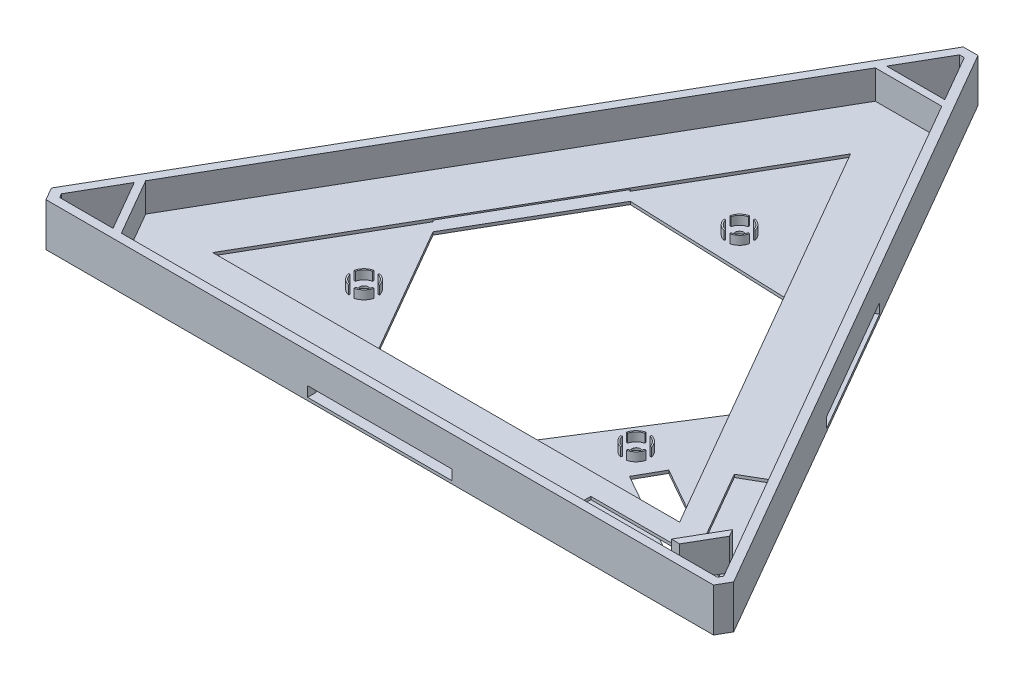
SolidWorks part; units mm, degrees
ref_plane "Front Plane" through (0, 0, 0) normal (0, 0, 1) x (1, 0, 0)
ref_plane "Top Plane" through (0, 0, 0) normal (0, 1, 0) x (1, 0, 0)
ref_plane "Right Plane" through (0, 0, 0) normal (1, 0, 0) x (0, 0, -1)
sketch "Sketch1" plane through (0, 0, 0) normal (0, 1, 0) x (1, 0, 0)
  line L0 (351.2729, 67.6655) -> (468.273, -134.9846)
  line L1 (347.2728, 67.6655) -> (347.2728, 65.1655) construction
  line L2 (409.773, -33.6595) -> (407.6079, -34.9095) construction
  line L3 (468.273, -134.9846) -> (464.2732, -141.9124)
  line L4 (230.2733, -141.9124) -> (464.2732, -141.9124)
  line L5 (230.2733, -141.9124) -> (226.2727, -134.9842)
  line L6 (226.2727, -134.9842) -> (343.2728, 67.6655)
  line L7 (353.4142, 63.9567) -> (351.2491, 62.7067) construction
  line L8 (347.2733, -141.9124) -> (347.2733, -139.4124) construction
  line L9 (231.7167, -139.4124) -> (462.8299, -139.4124)
  line L10 (284.7727, -33.6594) -> (286.9378, -34.9094) construction
  line L11 (344.7161, 65.1655) -> (349.8295, 65.1655)
  line L12 (465.3862, -134.9846) -> (349.8295, 65.1655)
  line L13 (466.2731, -138.4485) -> (464.1081, -137.1985) construction
  line L14 (462.8299, -139.4124) -> (465.3862, -134.9846)
  line L15 (229.1594, -134.9842) -> (344.7161, 65.1655)
  line L16 (229.1594, -134.9842) -> (231.7167, -139.4124)
  line L17 (286.9378, -34.9094) -> (287.3708, -35.1594) construction
  line L18 (230.438, -137.1983) -> (230.871, -136.9483) construction
  line L19 (232.0053, -138.9123) -> (229.7368, -134.9842)
  line L20 (343.2728, 67.6655) -> (351.2729, 67.6655)
  line L21 (345.0048, 64.6655) -> (229.7368, -134.9842)
  line L22 (349.5409, 64.6655) -> (345.0048, 64.6655)
  line L23 (249.0568, -126.4468) -> (246.8918, -127.697) construction
  line L24 (407.6079, -34.9095) -> (407.1749, -35.1595) construction
  line L26 (233.4463, -136.4089) -> (251.9226, -136.4093)
  line L27 (464.8089, -134.9846) -> (462.5412, -138.9123)
  line L28 (462.5412, -138.9123) -> (232.0053, -138.9123)
  line L29 (251.9226, -136.4093) -> (241.8609, -118.9847)
  line L30 (241.8609, -118.9847) -> (232.6236, -134.9842)
  line L31 (232.6236, -134.9842) -> (233.4463, -136.4089)
  line L33 (287.3708, -35.1594) -> (289.5359, -36.4094) construction
  line L34 (254.8093, -136.4089) -> (243.3042, -116.4848)
  line L35 (335.7675, 43.666) -> (243.3042, -116.4848)
  line L36 (358.7782, 43.666) -> (335.7675, 43.666)
  line L38 (289.5359, -36.4094) -> (306.8564, -46.4094) construction
  line L41 (461.939, -134.9846) -> (461.1164, -136.4093)
  line L42 (347.2688, -136.4172) -> (347.2688, -116.4172) construction
  line L43 (442.6021, -136.4093) -> (452.6999, -118.9847)
  line L44 (245.2636, -119.878) -> (249.0568, -126.4468) construction
  line L45 (452.6999, -118.9847) -> (461.939, -134.9846)
  line L48 (461.1164, -136.4093) -> (442.6021, -136.4093)
  line L49 (405.0134, -36.4027) -> (387.6936, -46.404) construction
  line L50 (306.8564, -46.4094) -> (466.2731, -138.4485) construction
  line L51 (357.3348, 46.166) -> (337.2109, 46.166)
  line L52 (337.2109, 46.166) -> (346.4484, 62.1659)
  line L53 (346.4484, 62.1659) -> (348.0966, 62.164)
  line L54 (348.0966, 62.164) -> (357.3348, 46.166)
  line L55 (228.273, -138.4483) -> (387.6936, -46.404) construction
  line L56 (347.2688, -116.4172) -> (347.2728, 43.666) construction
  line L57 (266.4391, -116.428) -> (428.1137, -116.4172)
  line L58 (347.2736, 23.6092) -> (428.1137, -116.4172)
  line L59 (266.4391, -116.428) -> (347.2736, 23.6092)
  line L60 (439.7283, -136.4254) -> (439.7283, -132.9254) construction
  line L61 (451.2487, -116.4715) -> (448.6507, -117.9717) construction
  line L62 (452.6999, -118.9847) -> (358.7782, 43.666)
  line L63 (442.6021, -136.4093) -> (254.8093, -136.4089)
  line L64 (441.749, -132.9254) -> (444.621, -132.9254)
  line L65 (448.6507, -117.9717) -> (450.9647, -121.979) construction
  line L66 (449.5167, -119.4714) -> (450.9647, -121.979)
  line L67 (441.749, -132.9254) -> (449.5167, -119.4714)
  line L68 (450.9647, -121.979) -> (444.621, -132.9254)
  line L69 (461.939, -134.9846) -> (427.2809, -114.9747) construction
  line L70 (461.1164, -136.4093) -> (426.4891, -116.4173) construction
  line L73 (405.0134, -134.9846) -> (439.7283, -134.9846)
  line L74 (405.0134, -134.9846) -> (405.0134, -124.0609)
  line L75 (405.0134, -124.0609) -> (439.7283, -124.0609)
  line L76 (439.7283, -134.9846) -> (439.7283, -124.0609)
  line L77 (405.0134, -124.0609) -> (430.3202, -80.2282) construction
  line L78 (405.0134, -134.9846) -> (433.4739, -85.6896) construction
  line L79 (461.1164, -136.4093) -> (424.3464, -72.7321) construction
  line L80 (432.6513, -87.1143) -> (423.1904, -92.5775)
  line L81 (432.6513, -87.1143) -> (450.1194, -117.365)
  line L82 (423.1904, -92.5775) -> (440.6585, -122.8281)
  line L83 (450.1194, -117.365) -> (440.6585, -122.8281)
  point P13 (407.6079, -34.9095)
  point P20 (464.1081, -137.1985)
  point P23 (347.2733, -139.4124)
  point P25 (347.2732, -141.9124)
  point P27 (347.2728, 65.1655)
  point P31 (286.9378, -34.9094)
  point P37 (287.3708, -35.1594)
  point P39 (230.871, -136.9483)
  point P41 (347.2728, 64.6655)
  point P45 (407.1749, -35.1595)
  point P50 (246.8918, -127.697)
  point P56 (289.5359, -36.4094)
  point P58 (249.0568, -126.4468)
  point P60 (347.2728, 43.666)
  point P62 (345.0048, -136.4089)
  point P64 (445.4885, -126.4485)
  point P71 (447.651, -127.697)
  point P77 (347.2728, 46.166)
  point P84 (347.2688, -116.4172)
  point P87 (387.6936, -46.404)
  point P89 (306.8564, -46.4094)
  point P100 (405.0134, -36.4027)
  dimension "D1" = 2.5
  dimension "D2" = 2.5
  dimension "D3" = 2.5
  dimension "D4" = 2.5
  dimension "D5" = 2.5
  dimension "D6" = 2.5
  dimension "D7" = 0.5
  dimension "D8" = 0.5
  dimension "D9" = 0.5
  dimension "D10" = 2.5
  dimension "D11" = 2.5
  dimension "D12" = 20
  dimension "D13" = 20
  dimension "D14" = 20
  dimension "D15" = 3.5
  dimension "D16" = 3
extrude "Boss-Extrude1" add sketch "Sketch1" along normal blind 1 contours L36 L35 L34 L57 L59 L58 region at (251.4484, 0, 125.0658)
extrude "Boss-Extrude2" add sketch "Sketch1<9>" along normal blind 11 contours L28 L27 L22 L21 L19 L31 L30 L29 L26 L34 L35 L36 L41 L48 L43 L45 L53 L54 L51 L52 | L68 L64 L67 L66 region at (230.7087, 0, 137.042)
sketch "Sketch1<9>" plane through (0, 0, 0) normal (0, 1, 0) x (1, 0, 0) same geometry as "Sketch1"
extrude "Boss-Extrude3" add sketch "Sketch1<10>" along normal blind 5 and the other way blind 3 contours L28 L27 L22 L21 L19 L31 L30 L29 L26 L34 L35 L36 L41 L48 L43 L45 L53 L54 L51 L52 region at (230.7087, 0, 137.042)
sketch "Sketch1<10>" plane through (0, 0, 0) normal (0, 1, 0) x (1, 0, 0) same geometry as "Sketch1"
sketch "Sketch3" plane through (290.5896, 0, -167.772) normal (0.866, 0, -0.5) x (-0.5, 0, -0.866)
  line L1 (-261.593, -6.5) -> (-211.593, -6.5)
  line L2 (-261.593, -6.5) -> (-261.593, 0.5)
  line L3 (-261.593, 0.5) -> (-211.593, 0.5)
  line L4 (-211.593, -6.5) -> (-211.593, 0.5)
  line L5 (-261.593, -6.5) -> (-211.593, 0.5) construction
  line L6 (-261.593, 0.5) -> (-211.593, -6.5) construction
  point P0 (-236.593, -3)
  dimension "D1" = 50
  dimension "D2" = 7
extrude "Cut-Extrude3" cut sketch "Sketch3" against normal blind 25
sketch "Sketch5" plane through (0, 0, 139.4124) normal (0, 0, 1) x (1, 0, 0)
  line L0 (231.7167, -3) -> (462.8299, -3) construction
  line L1 (322.2733, -6.5) -> (372.2733, -6.5)
  line L2 (322.2733, -6.5) -> (322.2733, 0.5)
  line L3 (322.2733, 0.5) -> (372.2733, 0.5)
  line L4 (372.2733, -6.5) -> (372.2733, 0.5)
  line L5 (322.2733, -6.5) -> (372.2733, 0.5) construction
  line L6 (322.2733, 0.5) -> (372.2733, -6.5) construction
  point P0 (347.2733, -3)
  dimension "D1" = 50
  dimension "D2" = 7
extrude "Cut-Extrude4" cut sketch "Sketch5" against normal blind 25
sketch "Sketch6" plane through (230.3194, 0, 132.9752) normal (-0.866, 0, -0.5) x (-0.5, 0, 0.866)
  line L0 (2.3199, -3) -> (-228.7932, -3) construction
  line L1 (-138.2367, -6.5) -> (-88.2367, -6.5)
  line L2 (-138.2367, -6.5) -> (-138.2367, 0.5)
  line L3 (-138.2367, 0.5) -> (-88.2367, 0.5)
  line L4 (-88.2367, -6.5) -> (-88.2367, 0.5)
  line L5 (-138.2367, -6.5) -> (-88.2367, 0.5) construction
  line L6 (-138.2367, 0.5) -> (-88.2367, -6.5) construction
  point P0 (-113.2367, -3)
  dimension "D1" = 50
  dimension "D2" = 7
extrude "Cut-Extrude5" cut sketch "Sketch6" against normal blind 25
sketch "Sketch8" plane through (0, -3, 0) normal (0, -1, 0) x (1, 0, 0)
  line L1 (349.8295, -65.1655) -> (465.3862, 134.9846)
  line L2 (465.3862, 134.9846) -> (462.8299, 139.4124)
  line L6 (462.8299, 139.4124) -> (231.7167, 139.4124)
  line L7 (450.147, 123.2807) -> (452.6999, 118.9847)
  line L9 (452.6999, 118.9847) -> (461.939, 134.9846)
  line L12 (461.939, 134.9846) -> (461.1164, 136.4093)
  line L17 (461.1164, 136.4093) -> (442.6021, 136.4093)
  line L19 (322.2733, 116.4243) -> (294.3582, 68.0611)
  line L20 (294.3582, 68.0611) -> (319.3545, 24.7577)
  line L21 (319.3545, 24.7577) -> (376.4737, 26.9694)
  line L22 (376.4737, 26.9694) -> (401.4727, 70.2712)
  line L23 (401.4727, 70.2712) -> (372.2733, 116.4209)
  line L24 (372.2733, 116.4209) -> (322.2733, 116.4243)
  line L25 (386.873, 93.3461) -> (395.3235, 98.6928) construction
  line L30 (308.3157, 92.2427) -> (299.6549, 97.2417) construction
  line L31 (347.9141, 25.8635) -> (348.3013, 15.8635) construction
  line L34 (401.698, 107.3846) -> (445.2267, 131.9864)
  line L35 (450.147, 123.2807) -> (406.6183, 98.6788)
  line L36 (401.698, 107.3846) -> (406.6183, 98.6788)
  line L37 (231.7167, 139.4124) -> (229.1594, 134.9842)
  line L39 (233.4463, 136.4089) -> (251.9226, 136.4093)
  line L40 (251.9226, 136.4093) -> (241.8609, 118.9847)
  line L41 (241.8609, 118.9847) -> (232.6236, 134.9842)
  line L42 (232.6236, 134.9842) -> (233.4463, 136.4089)
  line L43 (349.8295, -65.1655) -> (344.7161, -65.1655)
  line L44 (344.7161, -65.1655) -> (229.1594, 134.9842)
  line L45 (337.2109, -46.166) -> (357.3348, -46.166)
  line L46 (357.3348, -46.166) -> (348.0966, -62.164)
  line L47 (348.0966, -62.164) -> (346.4484, -62.1659)
  line L48 (346.4484, -62.1659) -> (337.2109, -46.166)
  line L49 (442.6021, 136.4093) -> (445.2267, 131.9864)
  circle A0 centre (395.3235, 98.6928) radius 1.5
  circle A1 centre (348.3013, 15.8635) radius 1.5
  circle A2 centre (299.6549, 97.2417) radius 1.5
  dimension "D6" = 3
  dimension "D7" = 3
  dimension "D8" = 3
  dimension "D1" = 10
  dimension "D2" = 50
  dimension "D3" = 10
  dimension "D4" = 10
  dimension "D5" = 10
extrude "Boss-Extrude5" add sketch "Sketch8" along normal blind 1
sketch "Sketch12" plane through (0, -3, 0) normal (0, 1, 0) x (1, 0, 0)
  line L0 (348.3013, -11.8635) -> (348.3013, -11.3635) construction
  line L1 (348.3013, -11.3635) -> (349.2951, -11.4746) construction
  line L2 (349.2951, -11.4746) -> (349.1847, -11.9623)
  line L3 (348.3013, -11.3635) -> (347.3075, -11.4746) construction
  line L4 (347.3075, -11.4746) -> (347.4179, -11.9623)
  line L5 (352.3013, -15.8635) -> (352.8013, -15.8635) construction
  line L6 (344.3013, -15.8635) -> (343.8013, -15.8635) construction
  line L7 (348.3013, -19.8635) -> (348.3013, -20.3635) construction
  line L8 (352.8013, -15.8635) -> (352.6902, -14.8697) construction
  line L9 (352.8013, -15.8635) -> (352.6902, -16.8573) construction
  line L10 (343.8013, -15.8635) -> (343.9124, -14.8697) construction
  line L11 (343.8013, -15.8635) -> (343.9124, -16.8573) construction
  line L12 (348.3013, -20.3635) -> (349.2951, -20.2524) construction
  line L13 (348.3013, -20.3635) -> (347.3075, -20.2524) construction
  line L14 (343.9124, -14.8697) -> (348.3013, -15.8635) construction
  line L15 (348.3013, -15.8635) -> (352.6902, -14.8697) construction
  line L16 (343.9124, -16.8573) -> (348.3013, -15.8635) construction
  line L17 (348.3013, -15.8635) -> (352.6902, -16.8573) construction
  line L18 (347.3075, -20.2524) -> (348.3013, -15.8635) construction
  line L19 (348.3013, -15.8635) -> (349.2951, -20.2524) construction
  line L20 (343.9124, -14.8697) -> (344.4001, -14.9801)
  line L21 (343.9124, -16.8573) -> (344.4001, -16.7469)
  line L22 (347.3075, -20.2524) -> (347.4179, -19.7648)
  line L23 (349.2951, -20.2524) -> (349.1847, -19.7648)
  line L24 (352.6902, -14.8697) -> (352.2025, -14.9801)
  line L25 (352.6902, -16.8573) -> (352.2025, -16.7469)
  line L26 (395.3235, -94.1928) -> (395.3235, -98.6928) construction
  line L27 (395.3235, -98.6928) -> (390.8235, -98.6928) construction
  line L28 (390.8235, -98.6928) -> (390.9347, -97.699) construction
  line L29 (399.8235, -98.6928) -> (395.3235, -98.6928) construction
  line L30 (395.3235, -98.6928) -> (395.3235, -103.1928) construction
  line L31 (395.3235, -103.1928) -> (396.3173, -103.0817) construction
  line L32 (395.3235, -94.1928) -> (396.3173, -94.3039) construction
  line L33 (395.3235, -94.1928) -> (394.3297, -94.3039) construction
  line L34 (399.7124, -97.699) -> (399.8235, -98.6928) construction
  line L35 (399.8235, -98.6928) -> (399.7124, -99.6866) construction
  line L36 (390.9347, -99.6866) -> (390.8235, -98.6928) construction
  line L37 (394.3297, -103.0817) -> (395.3235, -103.1928) construction
  line L38 (394.3297, -94.3039) -> (395.3235, -98.6928) construction
  line L39 (395.3235, -98.6928) -> (396.3173, -94.3039) construction
  line L40 (390.9347, -99.6866) -> (395.3235, -98.6928) construction
  line L41 (395.3235, -98.6928) -> (390.9347, -97.699) construction
  line L42 (399.7124, -97.699) -> (395.3235, -98.6928) construction
  line L43 (395.3235, -98.6928) -> (399.7124, -99.6866) construction
  line L44 (394.3297, -103.0817) -> (395.3235, -98.6928) construction
  line L45 (395.3235, -98.6928) -> (396.3173, -103.0817) construction
  line L46 (394.3297, -94.3039) -> (394.4402, -94.7916)
  line L47 (396.3173, -94.3039) -> (396.2069, -94.7916)
  line L48 (399.7124, -97.699) -> (399.2248, -97.8094)
  line L49 (399.7124, -99.6866) -> (399.2248, -99.5762)
  line L50 (396.3173, -103.0817) -> (396.2069, -102.5941)
  line L51 (394.3297, -103.0817) -> (394.4402, -102.5941)
  line L52 (390.9347, -99.6866) -> (391.4223, -99.5762)
  line L53 (390.9347, -97.699) -> (391.4248, -97.7985)
  line L54 (299.6549, -92.7417) -> (299.6549, -97.2417) construction
  line L55 (299.6549, -97.2417) -> (304.1549, -97.2417) construction
  line L56 (299.6549, -101.7417) -> (299.6549, -97.2417) construction
  line L57 (299.6549, -97.2417) -> (295.1549, -97.2417) construction
  line L58 (299.6549, -97.2417) -> (298.6611, -92.8528) construction
  line L59 (298.6611, -92.8528) -> (299.6549, -92.7417) construction
  line L60 (299.6549, -92.7417) -> (300.6487, -92.8528) construction
  line L61 (300.6487, -92.8528) -> (299.6549, -97.2417) construction
  line L62 (299.6549, -97.2417) -> (304.0438, -96.2479) construction
  line L63 (304.0438, -96.2479) -> (304.1549, -97.2417) construction
  line L64 (304.1549, -97.2417) -> (304.0438, -98.2355) construction
  line L65 (304.0438, -98.2355) -> (299.6549, -97.2417) construction
  line L66 (299.6549, -97.2417) -> (300.6487, -101.6306) construction
  line L67 (300.6487, -101.6306) -> (299.6549, -101.7417) construction
  line L68 (299.6549, -101.7417) -> (298.6611, -101.6306) construction
  line L69 (298.6611, -101.6306) -> (299.6549, -97.2417) construction
  line L70 (299.6549, -97.2417) -> (295.266, -98.2355) construction
  line L71 (295.266, -98.2355) -> (295.1549, -97.2417) construction
  line L72 (295.1549, -97.2417) -> (295.266, -96.2479) construction
  line L73 (295.266, -96.2479) -> (299.6549, -97.2417) construction
  line L74 (295.266, -96.2479) -> (295.7537, -96.3583)
  line L75 (295.266, -98.2355) -> (295.7537, -98.1251)
  line L76 (298.6611, -101.6306) -> (298.7715, -101.1429)
  line L77 (300.6487, -101.6306) -> (300.5383, -101.1429)
  line L78 (304.0438, -98.2355) -> (303.5561, -98.1251)
  line L79 (304.0438, -96.2479) -> (303.5561, -96.3583)
  line L80 (300.6487, -92.8528) -> (300.5383, -93.3404)
  line L81 (298.6611, -92.8528) -> (298.7715, -93.3404)
  circle A0 centre (348.3013, -15.8635) radius 4.5
  circle A1 centre (395.3235, -98.6928) radius 4.5
  circle A2 centre (299.6549, -97.2417) radius 4.5
  circle A3 centre (348.3013, -15.8635) radius 4
  circle A4 centre (395.3235, -98.6928) radius 4
  circle A5 centre (299.6549, -97.2417) radius 4
  dimension "D1" = 9
  dimension "D2" = 9
  dimension "D3" = 9
  dimension "D4" = 8
  dimension "D5" = 8
  dimension "D6" = 8
  dimension "D7" = 1
  dimension "D8" = 1
  dimension "D9" = 1
  dimension "D10" = 1
  dimension "D11" = 1
  dimension "D12" = 1
  dimension "D13" = 1
  dimension "D14" = 1
  dimension "D15" = 1
  dimension "D16" = 1
  dimension "D17" = 1
  dimension "D18" = 1
  dimension "D19" = 1
  dimension "D20" = 1
  dimension "D21" = 1
  dimension "D22" = 1
  dimension "D23" = 1
  dimension "D24" = 1
  dimension "D25" = 1
  dimension "D26" = 1
  dimension "D27" = 1
  dimension "D28" = 1
  dimension "D29" = 1
  dimension "D30" = 1
extrude "Boss-Extrude10" add sketch "Sketch12" along normal blind 3 contours A3 L4 A0 L20 | A3 L24 A0 L2 | A3 L23 A0 L25 | A3 L21 A0 L22 | A4 L46 A1 L53 | A4 L48 A1 L47 | A4 L50 A1 L49 | A4 L52 A1 L51 | A5 L81 A2 L74 | A5 L79 A2 L80 | A5 L77 A2 L78 | A5 L75 A2 L76 region at (351.1537, -3, 13.0111) region at (345.4489, -3, 13.0111) region at (351.1537, -3, 18.7159) region at (345.4489, -3, 18.7159) region at (392.4726, -3, 95.8382) region at (398.1759, -3, 95.8404) region at (392.4712, -3, 101.5452) region at (398.1759, -3, 101.5452) region at (296.8025, -3, 94.3893) region at (296.8025, -3, 100.0941) region at (302.5073, -3, 94.3893) region at (302.5073, -3, 100.0941)
